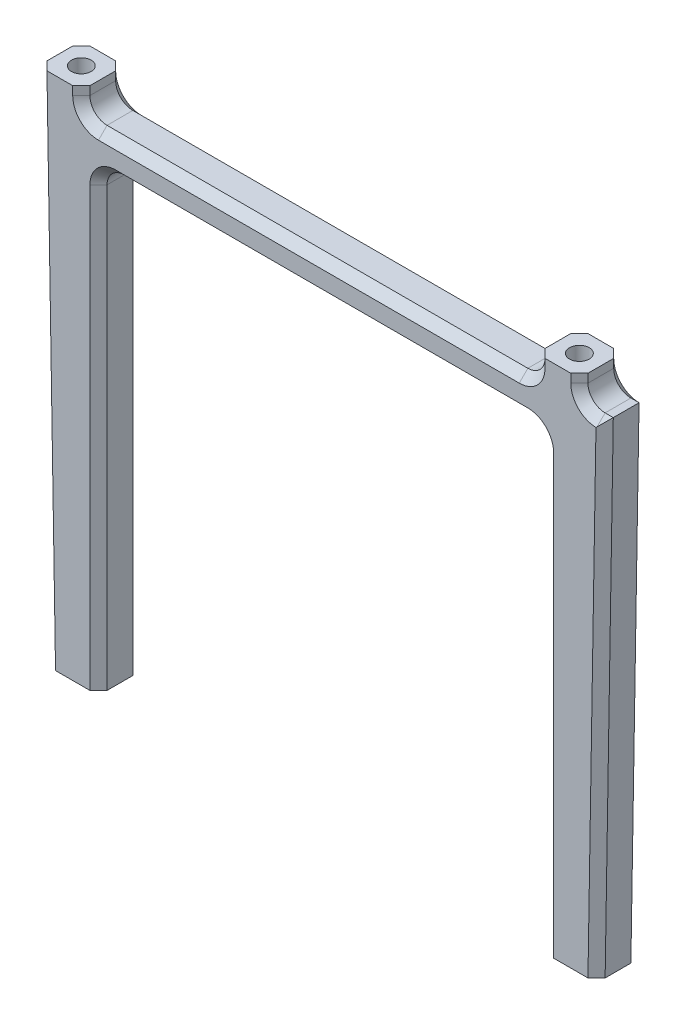
SolidWorks part; units mm, degrees
material "PLA"
ref_plane "Front Plane" through (0, 0, 0) normal (0, 0, 1) x (1, 0, 0)
ref_plane "Top Plane" through (0, 0, 0) normal (0, 1, 0) x (1, 0, 0)
ref_plane "Right Plane" through (0, 0, 0) normal (1, 0, 0) x (0, 0, -1)
sketch "Sketch1" plane through (0, 0, 0) normal (0, 0, 1) x (1, 0, 0)
  line L8 (0, 0) -> (-25, 0)
  line L9 (-25, 0) -> (-25, 3)
  line L10 (-25, 3) -> (-33, 3)
  line L11 (-33, 3) -> (-32, -56.9917)
  line L12 (-32, -56.9917) -> (-26, -56.9917)
  line L13 (-26, -56.9917) -> (-26, -4)
  line L14 (-26, -4) -> (0, -4)
  line L15 (0, -4) -> (0, 0)
  line L16 (0, 0) -> (0, 27.3851) construction
  point P2 (-29, -56.9917)
  point P8 (-29, 3)
  dimension "D1" = 58
  dimension "D2" = 60
  dimension "D3" = 8
  dimension "D4" = 4
  dimension "D5" = 3
  dimension "D6" = 6
extrude "Boss-Extrude1" add sketch "Sketch1" along normal blind 5
hole_wizard "Ø3.0mm Dowel Hole1" positions "Sketch4" profile "Sketch5" hole size "Ø3.0" standard "ISO"
sketch "Sketch4" plane through (0, -56.9917, 0) normal (0, -1, 0) x (-1, 0, 0)
  line L0 (26, -5) -> (26, 0) construction
  line L1 (32, -5) -> (26, -5) construction
  point P0 (29, -2.5)
  point P6 (26, -2.5)
  point P10 (29, -5)
sketch "Sketch5" plane through (-29, -56.9917, 2.5) normal (1, 0, 0) x (0, 0, -1)
  line L0 (0, 0) -> (0, 10.8412)
  line L1 (0, 10.8412) -> (1.4, 10)
  line L2 (1.4, 10) -> (1.4, 0.6)
  line L3 (1.4, 0.6) -> (2, 0)
  line L5 (2, 0) -> (0, 0)
  line L6 (-1.4, 0.6) -> (-2, 0) construction
  line L10 (0, 10.8412) -> (-1.4, 10) construction
  line L11 (0, -6.35) -> (0, 107.95) construction
  dimension "Hole Dia." = 2.8
  dimension "Hole Depth" = 10
  dimension "Near C'Sink Dia." = 4
  dimension "Near C'Sink Angle" = 90
  dimension "Drill Angle" = 118
mirror "Mirror1" about plane through (0, -4, 5) normal (-1, 0, 0) of bodies 103
hole_wizard "Ø2.5mm Dowel Hole1" positions "Sketch2" profile "Sketch3" hole size "Ø2.5" standard "ISO"
sketch "Sketch2" plane through (0, 3, 0) normal (0, 1, 0) x (1, 0, 0)
  line L0 (-25, -5) -> (-25, 0) construction
  line L1 (-25, 0) -> (-33, 0) construction
  point P0 (-30.5, -2.5)
  point P6 (-25, -2.5)
  point P10 (-29, 0)
  point P12 (27.5, -2.5)
  dimension "D1" = 58
  dimension "D2" = 1.5
sketch "Sketch3" plane through (-30.5, 3, 2.5) normal (1, 0, 0) x (0, 0, 1)
  line L0 (0, 0) -> (0, 10.691)
  line L1 (0, 10.691) -> (1.15, 10)
  line L2 (1.15, 10) -> (1.15, 0)
  line L5 (1.15, 0) -> (0, 0)
  line L10 (0, 10.691) -> (-1.15, 10) construction
  line L11 (0, -6.35) -> (0, 107.95) construction
  dimension "Hole Dia." = 2.3
  dimension "Hole Depth" = 10
  dimension "Drill Angle" = 118
sketch "Sketch6" plane through (0, 0, 5) normal (0, 0, 1) x (1, 0, 0)
  line L0 (-28, 3) -> (-28, 0)
  line L1 (-25, 3) -> (-33, 3) construction
  line L2 (-28, 0) -> (-25, 0)
  line L3 (-25, 0) -> (-25, 3)
  line L4 (-25, 3) -> (-28, 3)
  line L5 (-28, 3) -> (-30.5, 3) construction
  line L6 (-30.5, 3) -> (-33, 3) construction
  line L7 (-29.35, 3) -> (-31.65, 3) construction
  line L8 (30, 3) -> (27.5, 3) construction
  line L9 (33, 3) -> (30, 3)
  line L10 (33, 3) -> (33, 0)
  line L11 (33, 0) -> (30, 0)
  line L12 (30, 3) -> (30, 0)
  line L13 (25, 3) -> (33, 3) construction
  line L14 (27.5, 3) -> (25, 3) construction
  line L15 (28.65, 3) -> (26.35, 3) construction
  line L16 (25, 0) -> (-25, 0) construction
extrude "Cut-Extrude1" cut sketch "Sketch6" against normal up to next
fillet "Fillet2" radius 2 5 edges at (26, -4, 2.5) (-26, -4, 2.5) (25, 0, 2.5) (30, 0, 2.5) (-28, 0, 2.5)
chamfer "Chamfer1" distance 1 angle 45 28 edges at (25, 2.5, 0) (24.4142, 0.5858, 0) (-1.5, 0, 0) (25, 2.5, 5) (24.4142, 0.5858, 5) (-1.5, 0, 5) (-32.5, -26.9958, 5) (-32.5, -26.9958, 0) (-26, -31.4958, 5) (-25.4142, -4.5858, 5) (0, -4, 5) (25.4142, -4.5858, 5) (26, -31.4958, 5) (32.475, -28.4958, 5) (32.475, -28.4958, 0) (-26, -31.4958, 0) (-25.4142, -4.5858, 0) (0, -4, 0) (25.4142, -4.5858, 0) (26, -31.4958, 0) (-28, 2.5, 0) (-27.4142, 0.5858, 0) (-28, 2.5, 5) (-27.4142, 0.5858, 5) (30, 2.5, 0) (30.5858, 0.5858, 0) (30, 2.5, 5) (30.5858, 0.5858, 5)
other "Freeze***"
